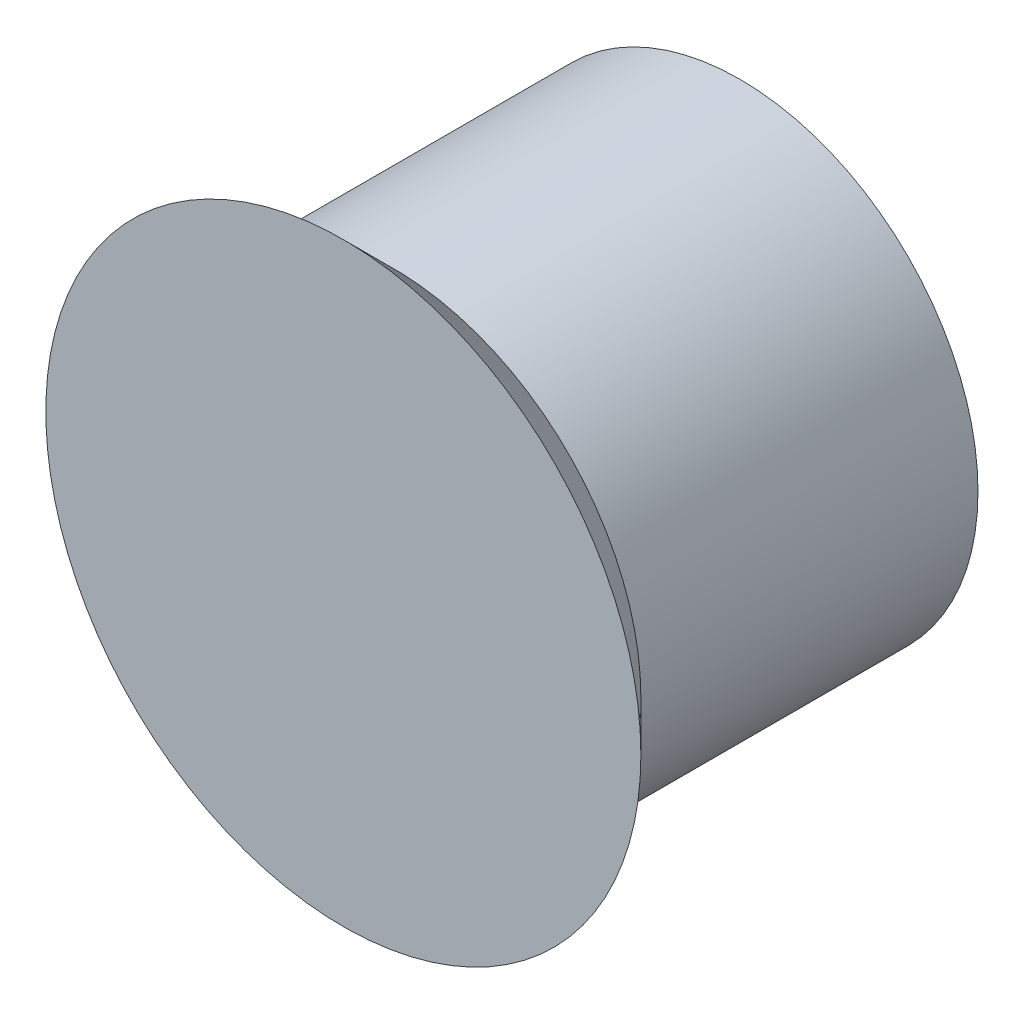
SolidWorks part; units mm, degrees
ref_plane "Ön Düzlem" through (0, 0, 0) normal (0, 0, 1) x (1, 0, 0)
ref_plane "Üst Düzlem" through (0, 0, 0) normal (0, 1, 0) x (1, 0, 0)
ref_plane "Sağ Düzlem" through (0, 0, 0) normal (1, 0, 0) x (0, 0, -1)
sketch "Çizim1" plane through (0, 0, 0) normal (0, 0, 1) x (1, 0, 0)
  circle A0 centre (0, 0) radius 2.4
  dimension "D1" = 4.8
extrude "Yükseklik-Ekstrüzyon1" add sketch "Çizim1" along normal blind 3.5
sketch "Çizim2" plane through (0, 0, 3.5) normal (0, 0, 1) x (1, 0, 0)
  circle A0 centre (0, 0) radius 2.5005
extrude "Yükseklik-Ekstrüzyon2" add sketch "Çizim2" along normal blind 0.5 draft 45 draft outward yes
